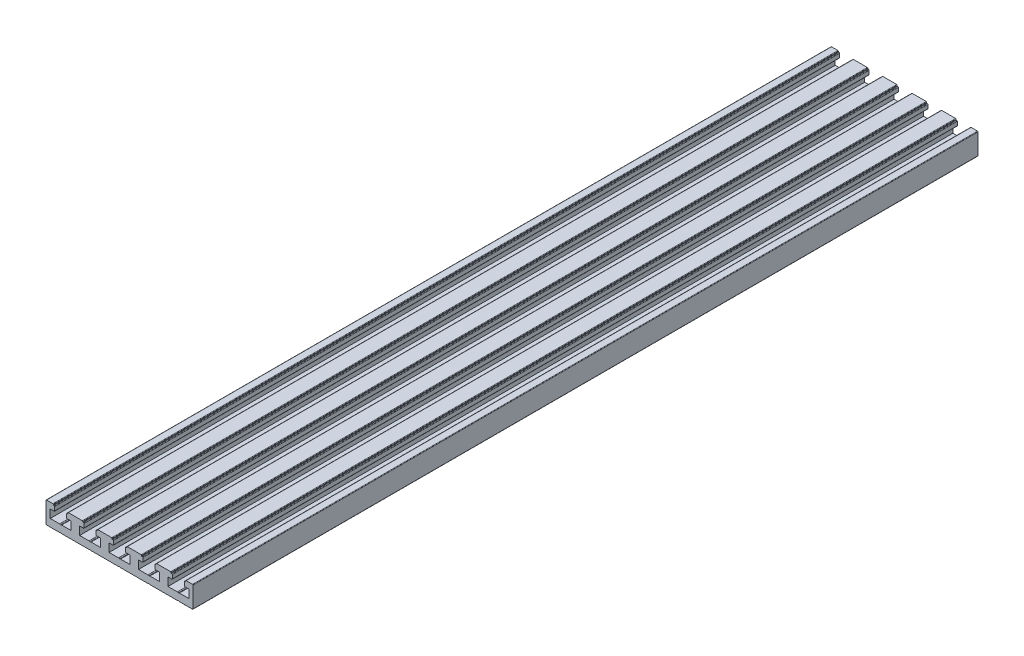
SolidWorks part; units mm, degrees
material "6061-T6 (SS)"
ref_plane "Front Plane" through (0, 0, 0) normal (0, 0, 1) x (1, 0, 0)
ref_plane "Top Plane" through (0, 0, 0) normal (0, 1, 0) x (1, 0, 0)
ref_plane "Right Plane" through (0, 0, 0) normal (1, 0, 0) x (0, 0, -1)
sketch "Sketch1" plane through (0, 0, 0) normal (0, 0, -1) x (-1, 0, 0)
  line L0 (0, 1.72) -> (0, -1.72) construction
  line L1 (-37.45, 8.85) -> (-37.45, -1.65)
  line L2 (-37.2, -1.9) -> (-30.5436, -1.9)
  line L3 (-30.4589, -1.8852) -> (-30, -1.72)
  line L4 (-30, -1.72) -> (-29.5411, -1.8852)
  line L5 (-29.4564, -1.9) -> (-15.5436, -1.9)
  line L6 (-15.4589, -1.8852) -> (-15, -1.72)
  line L7 (-15, -1.72) -> (-14.5411, -1.8852)
  line L8 (-14.4564, -1.9) -> (-0.5436, -1.9)
  line L9 (-0.4589, -1.8852) -> (0, -1.72)
  line L10 (0, -1.72) -> (0.4589, -1.8852)
  line L11 (0.5436, -1.9) -> (14.4564, -1.9)
  line L12 (14.5411, -1.8852) -> (15, -1.72)
  line L13 (15, -1.72) -> (15.4589, -1.8852)
  line L14 (15.5436, -1.9) -> (29.4564, -1.9)
  line L15 (29.5411, -1.8852) -> (30, -1.72)
  line L16 (30, -1.72) -> (30.4589, -1.8852)
  line L17 (30.5436, -1.9) -> (37.2, -1.9)
  line L18 (37.45, -1.65) -> (37.45, 8.85)
  line L19 (37.2, 9.1) -> (33.95, 9.1)
  line L20 (33.7, 8.85) -> (33.7, 8.5)
  line L21 (33.7, 8.5) -> (33.32, 8.5)
  line L22 (33.07, 8.25) -> (33.07, 6.35)
  line L23 (33.32, 6.1) -> (35.3, 6.1)
  line L24 (35.3, 6.1) -> (35.3, 1.9)
  line L25 (35.3, 1.9) -> (30.5436, 1.9)
  line L26 (30.4589, 1.8852) -> (30, 1.72)
  line L27 (30, 1.72) -> (29.5411, 1.8852)
  line L28 (29.4564, 1.9) -> (24.7, 1.9)
  line L29 (24.7, 1.9) -> (24.7, 6.1)
  line L30 (24.7, 6.1) -> (26.68, 6.1)
  line L31 (26.93, 6.35) -> (26.93, 8.25)
  line L32 (26.68, 8.5) -> (26.3, 8.5)
  line L33 (26.3, 8.5) -> (26.3, 8.85)
  line L34 (26.05, 9.1) -> (18.95, 9.1)
  line L35 (18.7, 8.85) -> (18.7, 8.5)
  line L36 (18.7, 8.5) -> (18.32, 8.5)
  line L37 (18.07, 8.25) -> (18.07, 6.35)
  line L38 (18.32, 6.1) -> (20.3, 6.1)
  line L39 (20.3, 6.1) -> (20.3, 1.9)
  line L40 (20.3, 1.9) -> (15.5436, 1.9)
  line L41 (15.4589, 1.8852) -> (15, 1.72)
  line L42 (15, 1.72) -> (14.5411, 1.8852)
  line L43 (14.4564, 1.9) -> (9.7, 1.9)
  line L44 (9.7, 1.9) -> (9.7, 6.1)
  line L45 (9.7, 6.1) -> (11.68, 6.1)
  line L46 (11.93, 6.35) -> (11.93, 8.25)
  line L47 (11.68, 8.5) -> (11.3, 8.5)
  line L48 (11.3, 8.5) -> (11.3, 8.85)
  line L49 (11.05, 9.1) -> (3.95, 9.1)
  line L50 (3.7, 8.85) -> (3.7, 8.5)
  line L51 (3.7, 8.5) -> (3.32, 8.5)
  line L52 (3.07, 8.25) -> (3.07, 6.35)
  line L53 (3.32, 6.1) -> (5.3, 6.1)
  line L54 (5.3, 6.1) -> (5.3, 1.9)
  line L55 (5.3, 1.9) -> (0.5436, 1.9)
  line L56 (0.4589, 1.8852) -> (0, 1.72)
  line L57 (0, 1.72) -> (-0.4589, 1.8852)
  line L58 (-0.5436, 1.9) -> (-5.3, 1.9)
  line L59 (-5.3, 1.9) -> (-5.3, 6.1)
  line L60 (-5.3, 6.1) -> (-3.32, 6.1)
  line L61 (-3.07, 6.35) -> (-3.07, 8.25)
  line L62 (-3.32, 8.5) -> (-3.7, 8.5)
  line L63 (-3.7, 8.5) -> (-3.7, 8.85)
  line L64 (-3.95, 9.1) -> (-11.05, 9.1)
  line L65 (-11.3, 8.85) -> (-11.3, 8.5)
  line L66 (-11.3, 8.5) -> (-11.68, 8.5)
  line L67 (-11.93, 8.25) -> (-11.93, 6.35)
  line L68 (-11.68, 6.1) -> (-9.7, 6.1)
  line L69 (-9.7, 6.1) -> (-9.7, 1.9)
  line L70 (-9.7, 1.9) -> (-14.4564, 1.9)
  line L71 (-14.5411, 1.8852) -> (-15, 1.72)
  line L72 (-15, 1.72) -> (-15.4589, 1.8852)
  line L73 (-15.5436, 1.9) -> (-20.3, 1.9)
  line L74 (-20.3, 1.9) -> (-20.3, 6.1)
  line L75 (-20.3, 6.1) -> (-18.32, 6.1)
  line L76 (-18.07, 6.35) -> (-18.07, 8.25)
  line L77 (-18.32, 8.5) -> (-18.7, 8.5)
  line L78 (-18.7, 8.5) -> (-18.7, 8.85)
  line L79 (-18.95, 9.1) -> (-26.05, 9.1)
  line L80 (-26.3, 8.85) -> (-26.3, 8.5)
  line L81 (-26.3, 8.5) -> (-26.68, 8.5)
  line L82 (-26.93, 8.25) -> (-26.93, 6.35)
  line L83 (-26.68, 6.1) -> (-24.7, 6.1)
  line L84 (-24.7, 6.1) -> (-24.7, 1.9)
  line L85 (-24.7, 1.9) -> (-29.4564, 1.9)
  line L86 (-29.5411, 1.8852) -> (-30, 1.72)
  line L87 (-30, 1.72) -> (-30.4589, 1.8852)
  line L88 (-30.5436, 1.9) -> (-35.3, 1.9)
  line L89 (-35.3, 1.9) -> (-35.3, 6.1)
  line L90 (-35.3, 6.1) -> (-33.32, 6.1)
  line L91 (-33.07, 6.35) -> (-33.07, 8.25)
  line L92 (-33.32, 8.5) -> (-33.7, 8.5)
  line L93 (-33.7, 8.5) -> (-33.7, 8.85)
  line L94 (-33.95, 9.1) -> (-37.2, 9.1)
  arc A0 (-37.45, -1.65) -> (-37.2, -1.9) centre (-37.2, -1.65) ccw
  arc A1 (-30.5436, -1.9) -> (-30.4589, -1.8852) centre (-30.5436, -1.65) ccw
  arc A2 (-29.5411, -1.8852) -> (-29.4564, -1.9) centre (-29.4564, -1.65) ccw
  arc A3 (-15.5436, -1.9) -> (-15.4589, -1.8852) centre (-15.5436, -1.65) ccw
  arc A4 (-14.5411, -1.8852) -> (-14.4564, -1.9) centre (-14.4564, -1.65) ccw
  arc A5 (-0.5436, -1.9) -> (-0.4589, -1.8852) centre (-0.5436, -1.65) ccw
  arc A6 (0.4589, -1.8852) -> (0.5436, -1.9) centre (0.5436, -1.65) ccw
  arc A7 (14.4564, -1.9) -> (14.5411, -1.8852) centre (14.4564, -1.65) ccw
  arc A8 (15.4589, -1.8852) -> (15.5436, -1.9) centre (15.5436, -1.65) ccw
  arc A9 (29.4564, -1.9) -> (29.5411, -1.8852) centre (29.4564, -1.65) ccw
  arc A10 (30.4589, -1.8852) -> (30.5436, -1.9) centre (30.5436, -1.65) ccw
  arc A11 (37.2, -1.9) -> (37.45, -1.65) centre (37.2, -1.65) ccw
  arc A12 (37.45, 8.85) -> (37.2, 9.1) centre (37.2, 8.85) ccw
  arc A13 (33.95, 9.1) -> (33.7, 8.85) centre (33.95, 8.85) ccw
  arc A14 (33.32, 8.5) -> (33.07, 8.25) centre (33.32, 8.25) ccw
  arc A15 (33.07, 6.35) -> (33.32, 6.1) centre (33.32, 6.35) ccw
  arc A16 (30.5436, 1.9) -> (30.4589, 1.8852) centre (30.5436, 1.65) ccw
  arc A17 (29.5411, 1.8852) -> (29.4564, 1.9) centre (29.4564, 1.65) ccw
  arc A18 (26.68, 6.1) -> (26.93, 6.35) centre (26.68, 6.35) ccw
  arc A19 (26.93, 8.25) -> (26.68, 8.5) centre (26.68, 8.25) ccw
  arc A20 (26.3, 8.85) -> (26.05, 9.1) centre (26.05, 8.85) ccw
  arc A21 (18.95, 9.1) -> (18.7, 8.85) centre (18.95, 8.85) ccw
  arc A22 (18.32, 8.5) -> (18.07, 8.25) centre (18.32, 8.25) ccw
  arc A23 (18.07, 6.35) -> (18.32, 6.1) centre (18.32, 6.35) ccw
  arc A24 (15.5436, 1.9) -> (15.4589, 1.8852) centre (15.5436, 1.65) ccw
  arc A25 (14.5411, 1.8852) -> (14.4564, 1.9) centre (14.4564, 1.65) ccw
  arc A26 (11.68, 6.1) -> (11.93, 6.35) centre (11.68, 6.35) ccw
  arc A27 (11.93, 8.25) -> (11.68, 8.5) centre (11.68, 8.25) ccw
  arc A28 (11.3, 8.85) -> (11.05, 9.1) centre (11.05, 8.85) ccw
  arc A29 (3.95, 9.1) -> (3.7, 8.85) centre (3.95, 8.85) ccw
  arc A30 (3.32, 8.5) -> (3.07, 8.25) centre (3.32, 8.25) ccw
  arc A31 (3.07, 6.35) -> (3.32, 6.1) centre (3.32, 6.35) ccw
  arc A32 (0.5436, 1.9) -> (0.4589, 1.8852) centre (0.5436, 1.65) ccw
  arc A33 (-0.4589, 1.8852) -> (-0.5436, 1.9) centre (-0.5436, 1.65) ccw
  arc A34 (-3.32, 6.1) -> (-3.07, 6.35) centre (-3.32, 6.35) ccw
  arc A35 (-3.07, 8.25) -> (-3.32, 8.5) centre (-3.32, 8.25) ccw
  arc A36 (-3.7, 8.85) -> (-3.95, 9.1) centre (-3.95, 8.85) ccw
  arc A37 (-11.05, 9.1) -> (-11.3, 8.85) centre (-11.05, 8.85) ccw
  arc A38 (-11.68, 8.5) -> (-11.93, 8.25) centre (-11.68, 8.25) ccw
  arc A39 (-11.93, 6.35) -> (-11.68, 6.1) centre (-11.68, 6.35) ccw
  arc A40 (-14.4564, 1.9) -> (-14.5411, 1.8852) centre (-14.4564, 1.65) ccw
  arc A41 (-15.4589, 1.8852) -> (-15.5436, 1.9) centre (-15.5436, 1.65) ccw
  arc A42 (-18.32, 6.1) -> (-18.07, 6.35) centre (-18.32, 6.35) ccw
  arc A43 (-18.07, 8.25) -> (-18.32, 8.5) centre (-18.32, 8.25) ccw
  arc A44 (-18.7, 8.85) -> (-18.95, 9.1) centre (-18.95, 8.85) ccw
  arc A45 (-26.05, 9.1) -> (-26.3, 8.85) centre (-26.05, 8.85) ccw
  arc A46 (-26.68, 8.5) -> (-26.93, 8.25) centre (-26.68, 8.25) ccw
  arc A47 (-26.93, 6.35) -> (-26.68, 6.1) centre (-26.68, 6.35) ccw
  arc A48 (-29.4564, 1.9) -> (-29.5411, 1.8852) centre (-29.4564, 1.65) ccw
  arc A49 (-30.4589, 1.8852) -> (-30.5436, 1.9) centre (-30.5436, 1.65) ccw
  arc A50 (-33.32, 6.1) -> (-33.07, 6.35) centre (-33.32, 6.35) ccw
  arc A51 (-33.07, 8.25) -> (-33.32, 8.5) centre (-33.32, 8.25) ccw
  arc A52 (-33.7, 8.85) -> (-33.95, 9.1) centre (-33.95, 8.85) ccw
  arc A53 (-37.2, 9.1) -> (-37.45, 8.85) centre (-37.2, 8.85) ccw
  point P2 (0, 0)
  dimension "D1" = 11
  dimension "D2" = 74.9
extrude "Base" add sketch "Sketch1" against normal blind 400
hole_wizard "CSK for M3 Flat Head Machine Screw1" positions "3DSketch1" profile "Sketch2" countersink size "M3" standard "ANSI Metric" end condition through all
sketch3d "3DSketch1"
  point P0 (-30, 1.9, 65)
  point P2 (30, 1.9, 65)
  point P35 (30, 1.9, 330)
  point P37 (-30, 1.9, 330)
  dimension "D4" = 330
  dimension "D1" = 65
  dimension "D2" = 7.45
  dimension "D3" = 60
sketch "Sketch2" plane through (-30, 1.9, 65) normal (1, 0, 0) x (0, 0, 1)
  line L0 (0, 0) -> (0, 3.8)
  line L1 (0, 3.8) -> (1.6, 3.8)
  line L2 (1.6, 3.8) -> (1.6, 1.4)
  line L3 (1.6, 1.4) -> (3, 0)
  line L5 (3, 0) -> (0, 0)
  line L6 (-1.6, 1.4) -> (-3, 0) construction
  line L11 (0, -6.35) -> (0, 107.95) construction
  dimension "Thru Hole Dia." = 3.2
  dimension "Thru Hole Depth" = 3.8
  dimension "Near C'Sink Dia." = 6
  dimension "Near C'Sink Angle" = 90
hole_wizard "M4x0.7 Tapped Hole1" positions "Sketch4" profile "Sketch5" tap size "M4x0.7" standard "ANSI Metric" end condition through all
sketch "Sketch4" plane through (0, 1.9, 0) normal (0, 1, 0) x (1, 0, 0)
  line L1 (-0.5436, 0) -> (-14.4564, 0) construction
  line L2 (-37.45, -400) -> (-37.45, 0) construction
  line L3 (15, -400) -> (15, 0) construction
  line L4 (37.2, -400) -> (30.5436, -400) construction
  point P0 (15, -30)
  point P15 (15, -371)
  dimension "D1" = 30
  dimension "D2" = 52.45
  dimension "D3" = 29
sketch "Sketch5" plane through (15, 1.9, 30) normal (1, 0, 0) x (0, 0, 1)
  line L0 (0, 0) -> (0, 3.8)
  line L1 (0, 3.8) -> (1.65, 3.8)
  line L2 (1.65, 3.8) -> (1.65, 0)
  line L5 (1.65, 0) -> (0, 0)
  line L11 (0, -6.35) -> (0, 107.95) construction
  dimension "Thru Tap Drill Dia." = 3.3
  dimension "Thru Tap Drill Depth" = 3.8
cosmetic thread "Hole Thread4" parameters "D2"=4
cosmetic thread "Hole Thread5" parameters "D2"=4
sketch "Sketch6" [suppressed] plane through (0, 0, 0) normal (0, 0, -1) x (-1, 0, 0)
  line L1 (-14.5411, -9.9057) -> (-41.3903, -9.9057)
  line L2 (-14.5411, -9.9057) -> (-14.5411, 14.5956)
  line L3 (-14.5411, 14.5956) -> (-41.3903, 14.5956)
  line L4 (-41.3903, -9.9057) -> (-41.3903, 14.5956)
extrude "Cut-Extrude1" [suppressed] cut sketch "Sketch6" against normal through all
equation "\"D4@3DSketch1\"=\"D1@Base\"-\"D1@3DSketch1\"-5"
